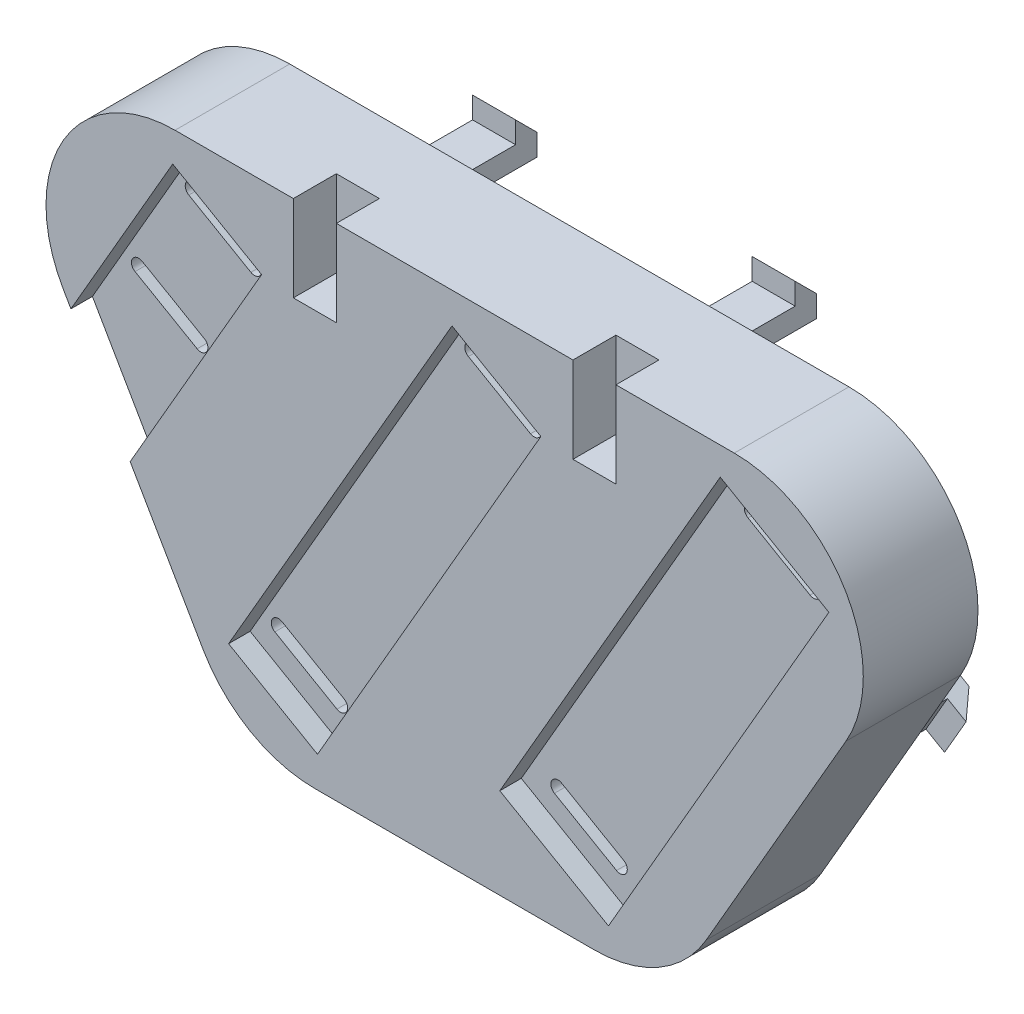
SolidWorks part; units mm, degrees
ref_plane "Front Plane" through (0, 0, 0) normal (0, 0, 1) x (1, 0, 0)
ref_plane "Top Plane" through (0, 0, 0) normal (0, 1, 0) x (1, 0, 0)
ref_plane "Right Plane" through (0, 0, 0) normal (1, 0, 0) x (0, 0, -1)
sketch "Sketch1" plane through (0, 0, 0) normal (0, 0, 1) x (1, 0, 0)
  line L0 (0, 0) -> (-19.5, 0) construction
  line L1 (-9.75, -16.8875) -> (-29.25, -16.8875) construction
  line L2 (0, 0) -> (-9.75, -16.8875) construction
  line L3 (-9.75, -16.8875) -> (-19.5, 0) construction
  line L4 (-19.5, 0) -> (-29.25, -16.8875) construction
  line L5 (-29.25, -16.8875) -> (-39, 0) construction
  line L6 (-39, 0) -> (-19.5, 0) construction
  line L7 (8.9827, 0.5584) -> (-5.4199, -24.3875) construction
  line L8 (-5.4199, -24.3875) -> (-33.5801, -24.3875) construction
  line L9 (-33.5801, -24.3875) -> (-47.9827, 0.5584) construction
  line L10 (-43.9749, 7.5) -> (4.9749, 7.5) construction
  line L11 (7.7942, -4.5) -> (-1.9558, -21.3875)
  line L12 (-9.75, -25.8875) -> (-29.25, -25.8875)
  line L13 (-37.0442, -21.3875) -> (-46.7942, -4.5)
  line L14 (-39, 9) -> (0, 9)
  line L15 (1.7814, -11.9145) -> (3.0804, -12.6645) construction
  line L16 (-19.5, -24.3875) -> (-19.5, -25.8875) construction
  line L17 (-40.7814, -11.9145) -> (-42.0804, -12.6645) construction
  line L18 (-19.5, 7.5) -> (-19.5, 9) construction
  circle A0 centre (-29.25, -16.8875) radius 7.5
  circle A1 centre (-19.5, 0) radius 7.5
  circle A2 centre (0, 0) radius 7.5
  circle A3 centre (0, 0) radius 7.5
  circle A4 centre (-9.75, -16.8875) radius 7.5
  circle A5 centre (-39, 0) radius 7.5
  arc A6 (7.7942, -4.5) -> (0, 9) centre (0, 0) ccw
  arc A7 (-39, 9) -> (-46.7942, -4.5) centre (-39, 0) ccw
  arc A8 (-1.9558, -21.3875) -> (-9.75, -25.8875) centre (-9.75, -16.8875) cw
  arc A9 (-29.25, -25.8875) -> (-37.0442, -21.3875) centre (-29.25, -16.8875) cw
  point P28 (1.7814, -11.9145)
  point P30 (-19.5, -24.3875)
  point P32 (-40.7814, -11.9145)
  point P35 (-19.5, 9)
  dimension "D2" = 15
  dimension "D3" = 19.5
  dimension "D4" = 1.5
  dimension "D5" = 1.5
  dimension "D1" = 0.25
extrude "Boss-Extrude1" add sketch "Sketch1" along normal blind 5
sketch "Sketch2" plane through (0, 0, 5) normal (0, 0, 1) x (1, 0, 0)
  line L0 (-1.9558, -21.3875) -> (7.7942, -4.5) construction
  line L1 (0, 9) -> (-39, 9) construction
  line L2 (-46.7942, -4.5) -> (-37.0442, -21.3875) construction
  line L3 (-29.25, -25.8875) -> (-9.75, -25.8875) construction
  line L4 (-1.9558, -21.3875) -> (7.7942, -4.5)
  line L5 (0, 9) -> (-39, 9)
  line L6 (-46.7942, -4.5) -> (-37.0442, -21.3875)
  line L7 (-29.25, -25.8875) -> (-9.75, -25.8875)
  line L8 (4.0401, 1.9976) -> (-0.2901, 4.4976) construction
  line L9 (3.7901, 1.5646) -> (-0.5401, 4.0646)
  line L10 (4.2901, 2.4306) -> (-0.0401, 4.9306)
  line L11 (-9.4599, -21.3851) -> (-13.7901, -18.8851) construction
  line L12 (-9.7099, -21.8181) -> (-14.0401, -19.3181)
  line L13 (-9.2099, -20.9521) -> (-13.5401, -18.4521)
  line L14 (1.875, 3.2476) -> (-11.625, -20.1351) construction
  line L15 (-31.125, -20.1351) -> (-29.25, -16.8875) construction
  line L16 (0, 0) -> (1.875, 3.2476) construction
  line L17 (1.875, 3.2476) -> (3.75, 6.4952) construction
  line L18 (-11.625, -20.1351) -> (-13.5, -23.3827) construction
  line L19 (-11.625, -20.1351) -> (-9.75, -16.8875) construction
  line L20 (-17.625, 3.2476) -> (-15.75, 6.4952) construction
  line L21 (-17.625, 3.2476) -> (-31.125, -20.1351) construction
  line L22 (-19.5, 0) -> (-17.625, 3.2476) construction
  line L23 (-31.125, -20.1351) -> (-33, -23.3827) construction
  line L24 (-15.4599, 1.9976) -> (-19.7901, 4.4976) construction
  line L25 (-15.7099, 1.5646) -> (-20.0401, 4.0646)
  line L26 (-15.2099, 2.4306) -> (-19.5401, 4.9306)
  line L27 (-28.9599, -21.3851) -> (-33.2901, -18.8851) construction
  line L28 (-29.2099, -21.8181) -> (-33.5401, -19.3181)
  line L29 (-28.7099, -20.9521) -> (-33.0401, -18.4521)
  line L30 (-34.9599, 1.9976) -> (-39.2901, 4.4976) construction
  line L31 (-35.2099, 1.5646) -> (-39.5401, 4.0646)
  line L32 (-34.7099, 2.4306) -> (-39.0401, 4.9306)
  line L33 (-38.7099, -4.4976) -> (-43.0401, -1.9976) construction
  line L34 (-38.9599, -4.9306) -> (-43.2901, -2.4306)
  line L35 (-38.4599, -4.0646) -> (-42.7901, -1.5646)
  line L36 (-37.125, 3.2476) -> (-40.875, -3.2476) construction
  line L37 (-37.125, 3.2476) -> (-35.25, 6.4952) construction
  line L38 (-40.875, -3.2476) -> (-42.75, -6.4952) construction
  line L39 (-37.125, 3.2476) -> (-39, 0) construction
  arc A0 (-9.75, -25.8875) -> (-1.9558, -21.3875) centre (-9.75, -16.8875) ccw construction
  arc A1 (7.7942, -4.5) -> (0, 9) centre (0, 0) ccw construction
  arc A2 (-39, 9) -> (-46.7942, -4.5) centre (-39, 0) ccw construction
  arc A3 (-37.0442, -21.3875) -> (-29.25, -25.8875) centre (-29.25, -16.8875) ccw construction
  arc A4 (-9.75, -25.8875) -> (-1.9558, -21.3875) centre (-9.75, -16.8875) ccw
  arc A5 (7.7942, -4.5) -> (0, 9) centre (0, 0) ccw
  arc A6 (-39, 9) -> (-46.7942, -4.5) centre (-39, 0) ccw
  arc A7 (-37.0442, -21.3875) -> (-29.25, -25.8875) centre (-29.25, -16.8875) ccw
  circle A8 centre (-39, 0) radius 7.5 construction
  circle A9 centre (-29.25, -16.8875) radius 7.5 construction
  circle A10 centre (-19.5, 0) radius 7.5 construction
  circle A11 centre (-9.75, -16.8875) radius 7.5 construction
  circle A12 centre (0, 0) radius 7.5 construction
  circle A13 centre (-39, 0) radius 7.5
  circle A14 centre (-29.25, -16.8875) radius 7.5
  circle A15 centre (-19.5, 0) radius 7.5
  circle A16 centre (-9.75, -16.8875) radius 7.5
  circle A17 centre (0, 0) radius 7.5
  arc A18 (3.7901, 1.5646) -> (4.2901, 2.4306) centre (4.0401, 1.9976) ccw
  arc A19 (-0.0401, 4.9306) -> (-0.5401, 4.0646) centre (-0.2901, 4.4976) ccw
  arc A20 (-9.7099, -21.8181) -> (-9.2099, -20.9521) centre (-9.4599, -21.3851) ccw
  arc A21 (-13.5401, -18.4521) -> (-14.0401, -19.3181) centre (-13.7901, -18.8851) ccw
  arc A22 (-15.7099, 1.5646) -> (-15.2099, 2.4306) centre (-15.4599, 1.9976) ccw
  arc A23 (-19.5401, 4.9306) -> (-20.0401, 4.0646) centre (-19.7901, 4.4976) ccw
  arc A24 (-29.2099, -21.8181) -> (-28.7099, -20.9521) centre (-28.9599, -21.3851) ccw
  arc A25 (-33.0401, -18.4521) -> (-33.5401, -19.3181) centre (-33.2901, -18.8851) ccw
  arc A26 (-35.2099, 1.5646) -> (-34.7099, 2.4306) centre (-34.9599, 1.9976) ccw
  arc A27 (-39.0401, 4.9306) -> (-39.5401, 4.0646) centre (-39.2901, 4.4976) ccw
  arc A28 (-38.9599, -4.9306) -> (-38.4599, -4.0646) centre (-38.7099, -4.4976) ccw
  arc A29 (-42.7901, -1.5646) -> (-43.2901, -2.4306) centre (-43.0401, -1.9976) ccw
  point P8 (-37.125, 3.2476)
  point P25 (1.875, 3.2476)
  point P32 (-11.625, -20.1351)
  point P45 (-17.625, 3.2476)
  point P52 (-31.125, -20.1351)
  point P64 (-40.875, -3.2476)
  circle M1 centre (-9.75, -16.8875) radius 7.5
  circle M2 centre (0, 0) radius 7.5
  arc M3 (7.7942, -4.5) -> (0, 9) centre (0, 0) ccw
  line M4 (0, 9) -> (-39, 9)
  arc M5 (-39, 9) -> (-46.7942, -4.5) centre (-39, 0) ccw
  line M6 (-46.7942, -4.5) -> (-37.0442, -21.3875)
  arc M7 (-37.0442, -21.3875) -> (-29.25, -25.8875) centre (-29.25, -16.8875) ccw
  line M8 (-29.25, -25.8875) -> (-9.75, -25.8875)
  arc M9 (-9.75, -25.8875) -> (-1.9558, -21.3875) centre (-9.75, -16.8875) ccw
  line M10 (-1.9558, -21.3875) -> (7.7942, -4.5)
  circle M11 centre (-19.5, 0) radius 7.5
  circle M12 centre (-29.25, -16.8875) radius 7.5
  circle M13 centre (-39, 0) radius 7.5
  dimension "D1" = 1
  dimension "D2" = 5
extrude "Boss-Extrude2" add sketch "Sketch2" along normal blind 1.5 contours A21 L13 A20 L12 M1 | M10 M3 M4 M5 M6 M7 M8 M9 M2 M11 M13 M12 M1 | A19 L10 A18 L9 M2 | A23 L26 A22 L25 M11 | A25 L29 A24 L28 M12 | A29 L35 A28 L34 A27 L32 A26 L31 M13 region at (-5.5841, -24.103, 5) region at (-39, 0, 5) region at (-29.1865, -16.7776, 5) region at (-19.5635, -0.1099, 5) region at (-9.6865, -16.7776, 5) region at (-0.0635, -0.1099, 5)
sketch "Sketch3" plane through (0, 0, 6.5) normal (0, 0, 1) x (1, 0, 0)
  line L0 (-46.7942, -4.5) -> (-37.0442, -21.3875) construction
  line L1 (-29.25, -25.8875) -> (-9.75, -25.8875) construction
  line L2 (-1.9558, -21.3875) -> (7.7942, -4.5) construction
  line L3 (0, 9) -> (-39, 9) construction
  line L4 (-46.7942, -4.5) -> (-37.0442, -21.3875)
  line L5 (-29.25, -25.8875) -> (-9.75, -25.8875)
  line L6 (-1.9558, -21.3875) -> (7.7942, -4.5)
  line L7 (0, 9) -> (-39, 9)
  line L8 (6.6014, 2.6839) -> (-8.7736, -23.9464)
  line L9 (6.6014, 2.6839) -> (-0.9764, 7.0589)
  line L10 (-8.7736, -23.9464) -> (-16.3514, -19.5714)
  line L11 (-0.9764, 7.0589) -> (-16.3514, -19.5714)
  line L12 (6.6014, 2.6839) -> (-16.3514, -19.5714) construction
  line L13 (-8.7736, -23.9464) -> (-0.9764, 7.0589) construction
  line L14 (-11.625, -20.1351) -> (-13.5, -23.3827) construction
  line L15 (-11.625, -20.1351) -> (-13.5, -23.3827) construction
  line L16 (-11.875, -20.5681) -> (-12.5625, -21.7589) construction
  line L17 (-9.7099, -21.8181) -> (-14.0401, -19.3181) construction
  line L18 (-14.2231, -18.6351) -> (-15.4139, -17.9476) construction
  line L19 (1.875, 3.2476) -> (-11.625, -20.1351) construction
  line L20 (1.875, 3.2476) -> (-11.625, -20.1351) construction
  line L21 (-31.125, -20.1351) -> (-33, -23.3827) construction
  line L22 (-17.625, 3.2476) -> (-31.125, -20.1351) construction
  line L23 (-31.125, -20.1351) -> (-33, -23.3827) construction
  line L24 (-17.625, 3.2476) -> (-31.125, -20.1351) construction
  line L25 (-13.4854, 3.2587) -> (-29.0648, -23.7257)
  line L26 (-13.4854, 3.2587) -> (-19.6852, 6.8382)
  line L27 (-29.0648, -23.7257) -> (-35.2646, -20.1462)
  line L28 (-19.6852, 6.8382) -> (-35.2646, -20.1462)
  line L29 (-13.4854, 3.2587) -> (-35.2646, -20.1462) construction
  line L30 (-29.0648, -23.7257) -> (-19.6852, 6.8382) construction
  line L31 (-32.8571, -19.1351) -> (-34.2249, -18.3454) construction
  line L32 (-31.375, -20.5681) -> (-32.1647, -21.9359) construction
  line L33 (-29.2099, -21.8181) -> (-33.5401, -19.3181) construction
  line L34 (-32.9626, 3.2982) -> (-42.1296, -12.5794)
  line L35 (-32.9626, 3.2982) -> (-39.1624, 6.8776)
  line L37 (-39.1624, 6.8776) -> (-46.2627, -5.4206)
  line L38 (-32.9626, 3.2982) -> (-45.5024, -6.7376) construction
  line L39 (-42.1296, -12.5794) -> (-39.1624, 6.8776) construction
  line L40 (-37.125, 3.2476) -> (-40.875, -3.2476) construction
  line L41 (-36.875, 3.6806) -> (-36.0625, 5.0879) construction
  line L42 (-34.7099, 2.4306) -> (-39.0401, 4.9306) construction
  line L43 (-36.0625, 5.0879) -> (-35.25, 6.4952) construction
  arc A0 (-37.0442, -21.3875) -> (-29.25, -25.8875) centre (-29.25, -16.8875) ccw construction
  arc A1 (-9.75, -25.8875) -> (-1.9558, -21.3875) centre (-9.75, -16.8875) ccw construction
  arc A2 (7.7942, -4.5) -> (0, 9) centre (0, 0) ccw construction
  arc A3 (-39, 9) -> (-46.7942, -4.5) centre (-39, 0) ccw construction
  arc A4 (-37.0442, -21.3875) -> (-29.25, -25.8875) centre (-29.25, -16.8875) ccw
  arc A5 (-9.75, -25.8875) -> (-1.9558, -21.3875) centre (-9.75, -16.8875) ccw
  arc A6 (7.7942, -4.5) -> (0, 9) centre (0, 0) ccw
  arc A7 (-39, 9) -> (-46.7942, -4.5) centre (-39, 0) ccw
  arc A8 (-13.5401, -18.4521) -> (-14.0401, -19.3181) centre (-13.7901, -18.8851) ccw construction
  arc A9 (-33.0401, -18.4521) -> (-33.5401, -19.3181) centre (-33.2901, -18.8851) ccw construction
  point P13 (-4.875, -8.4437)
  point P30 (-12.5625, -21.7589)
  point P33 (-4.875, -8.4437)
  point P35 (-24.375, -8.4437)
  point P49 (-24.375, -8.4437)
  point P50 (-40.646, -2.8509)
  line M15 (-1.9558, -21.3875) -> (7.7942, -4.5)
  arc M16 (7.7942, -4.5) -> (0, 9) centre (0, 0) ccw
  line M17 (0, 9) -> (-39, 9)
  arc M18 (-39, 9) -> (-46.7942, -4.5) centre (-39, 0) ccw
  line M19 (-46.7942, -4.5) -> (-37.0442, -21.3875)
  arc M20 (-37.0442, -21.3875) -> (-29.25, -25.8875) centre (-29.25, -16.8875) ccw
  line M21 (-29.25, -25.8875) -> (-9.75, -25.8875)
  arc M22 (-9.75, -25.8875) -> (-1.9558, -21.3875) centre (-9.75, -16.8875) ccw
extrude "Boss-Extrude3" add sketch "Sketch3" along normal blind 1.5 contours L37 L35 L34 L4 L28 L26 L25 L27 L11 L9 L8 L10 M20 M21 M22 M15 M16 M17 M18 M19 region at (-46.2155, 4.1659, 6.5)
sketch "Sketch4" plane through (0, 0, 0) normal (0, 0, -1) x (-1, 0, 0)
  line L0 (29.25, -25.8875) -> (9.75, -25.8875) construction
  line L1 (21, -25.8875) -> (18, -25.8875)
  line L2 (21, -25.8875) -> (21, -22.8875)
  line L3 (21, -22.8875) -> (18, -22.8875)
  line L4 (18, -25.8875) -> (18, -22.8875)
  line L5 (21, -25.8875) -> (18, -22.8875) construction
  line L6 (21, -22.8875) -> (18, -25.8875) construction
  line L7 (29.25, -25.8875) -> (9.75, -25.8875)
  line L8 (0, 9) -> (39, 9) construction
  line L9 (46.7942, -4.5) -> (37.0442, -21.3875) construction
  line L10 (1.9558, -21.3875) -> (-7.7942, -4.5) construction
  line L11 (0, 9) -> (39, 9)
  line L12 (46.7942, -4.5) -> (37.0442, -21.3875)
  line L13 (1.9558, -21.3875) -> (-7.7942, -4.5)
  line L14 (40.0712, -10.1447) -> (42.6692, -11.6447)
  line L15 (40.0712, -10.1447) -> (38.5712, -12.7428)
  line L16 (42.6692, -11.6447) -> (41.1692, -14.2428)
  line L17 (38.5712, -12.7428) -> (41.1692, -14.2428)
  line L18 (40.0712, -10.1447) -> (41.1692, -14.2428) construction
  line L19 (42.6692, -11.6447) -> (38.5712, -12.7428) construction
  line L20 (-1.0712, -10.1447) -> (-3.6692, -11.6447)
  line L21 (-1.0712, -10.1447) -> (0.4288, -12.7428)
  line L22 (-3.6692, -11.6447) -> (-2.1692, -14.2428)
  line L23 (0.4288, -12.7428) -> (-2.1692, -14.2428)
  line L24 (-1.0712, -10.1447) -> (-2.1692, -14.2428) construction
  line L25 (-3.6692, -11.6447) -> (0.4288, -12.7428) construction
  line L26 (41.9192, -12.9437) -> (3.9115, 9) construction
  line L27 (11.25, 6) -> (8.25, 6)
  line L28 (11.25, 6) -> (11.25, 9)
  line L29 (11.25, 9) -> (8.25, 9)
  line L30 (8.25, 6) -> (8.25, 9)
  line L31 (11.25, 6) -> (8.25, 9) construction
  line L32 (11.25, 9) -> (8.25, 6) construction
  line L33 (30.75, 6) -> (27.75, 6)
  line L34 (30.75, 6) -> (30.75, 9)
  line L35 (30.75, 9) -> (27.75, 9)
  line L36 (27.75, 6) -> (27.75, 9)
  line L37 (30.75, 6) -> (27.75, 9) construction
  line L38 (30.75, 9) -> (27.75, 6) construction
  line L39 (-2.9192, -12.9437) -> (35.0885, 9) construction
  point P0 (19.5, -24.3875)
  point P5 (9.75, 7.5)
  point P8 (19.5, -25.8875)
  point P15 (40.6202, -12.1937)
  point P16 (-1.6202, -12.1937)
  point P29 (29.25, 7.5)
  line M35 (9.75, -25.8875) -> (29.25, -25.8875)
  dimension "D1" = 3
  dimension "D2" = 3
extrude "Boss-Extrude4" add sketch "Sketch4" along normal blind 6 contours L15 L17 L12 L14 | L4 L2 L3 M35 | L23 L21 L20 L13 | L30 L27 L28 L11 | L36 L33 L34 L11 region at (-19.5, -24.3875, 0) region at (-29.25, 7.5, 0) region at (-9.75, 7.5, 0) region at (-40.6202, -12.1937, 0) region at (1.6202, -12.1937, 0)
sketch "Sketch5" plane through (-5.625, 9.7428, 0) normal (-0.5, 0.866, 0) x (0.866, 0.5, 0)
  line L0 (-42.775, 6) -> (-39.775, 6) construction
  line L1 (-42.775, 0) -> (-41.275, 0)
  line L2 (-42.775, 0) -> (-42.775, 4.5)
  line L3 (-42.775, 4.5) -> (-41.275, 4.5)
  line L4 (-41.275, 0) -> (-41.275, 4.5)
  line L5 (-42.775, 4.5) -> (-41.275, 6)
  point P9 (-41.275, 6)
  line M2 (-42.775, 0) -> (-39.775, 0)
  line M4 (-39.775, 6) -> (-42.775, 6)
  line M5 (-42.775, 6) -> (-42.775, 0)
  dimension "D1" = 4.5
extrude "Cut-Extrude1" cut sketch "Sketch5" against normal up to next contours L4 L3 M2 M5 | L5 M5 M4 region at (-42.0197, -11.2697, -2.25) region at (-42.2362, -11.3947, -5.5)
sketch "Sketch7" plane through (-30.75, 0, 0) normal (-1, 0, 0) x (0, 0, 1)
  line L0 (-6, 6) -> (-6, 9) construction
  line L1 (0, 9) -> (-4.5, 9)
  line L2 (0, 9) -> (0, 7.5)
  line L3 (0, 7.5) -> (-4.5, 7.5)
  line L4 (-4.5, 9) -> (-4.5, 7.5)
  line L5 (-4.5, 9) -> (-6, 7.5)
  point P9 (-6, 7.5)
  line M3 (0, 6) -> (0, 9)
  line M4 (0, 9) -> (-6, 9)
  line M5 (-6, 9) -> (-6, 6)
  dimension "D1" = 4.5
extrude "Cut-Extrude2" cut sketch "Sketch7" against normal up to next contours L4 L3 M4 M3 | L5 M4 M5 region at (-30.75, 8.25, -2.25) region at (-30.75, 8.5, -5.5)
ref_axis "Axis1" through (-19.5, -25.8875, -6) along (0, 0, 1)
ref_plane "Plane1" through (-19.5, 0, 0) normal (-1, 0, 0) x (0, 0, 1)
mirror "Mirror1" about plane through (-19.5, 0, 0) normal (-1, 0, 0) of "Cut-Extrude2", "Cut-Extrude1"
sketch "Sketch8" plane through (-21, 0, 0) normal (-1, 0, 0) x (0, 0, 1)
  line L0 (-4.5, -25.8875) -> (-6, -24.3875)
  line L1 (0, -25.8875) -> (-4.5, -25.8875)
  line L2 (0, -25.8875) -> (0, -24.3875)
  line L3 (0, -24.3875) -> (-4.5, -24.3875)
  line L4 (-4.5, -25.8875) -> (-4.5, -24.3875)
  line L5 (0, -25.8875) -> (0, -22.8875) construction
  line L6 (-6, -25.8875) -> (-6, -22.8875) construction
  line M2 (0, -25.8875) -> (0, -22.8875)
  line M4 (-6, -22.8875) -> (-6, -25.8875)
  line M5 (-6, -25.8875) -> (0, -25.8875)
  dimension "D1" = 4.5
extrude "Cut-Extrude3" cut sketch "Sketch8" against normal up to next contours L0 M5 M4 | L4 L3 M5 M2 region at (-21, -25.3875, -5.5) region at (-21, -25.1375, -2.25)
sketch "Sketch9" plane through (0, 0, 8) normal (0, 0, 1) x (1, 0, 0)
  line L0 (-39, 9) -> (-19.5, 9)
  line L1 (0, 9) -> (-39, 9) construction
  line L2 (-19.5, 9) -> (0, 9) construction
  line L3 (-29.25, 9) -> (-29.25, 3) construction
  line L4 (-27.75, 3) -> (-30.75, 3)
  line L5 (-27.75, 3) -> (-27.75, 9)
  line L6 (-27.75, 9) -> (-30.75, 9)
  line L7 (-30.75, 3) -> (-30.75, 9)
  line L8 (-27.75, 3) -> (-30.75, 9) construction
  line L9 (-27.75, 9) -> (-30.75, 3) construction
  line L10 (-8.25, 3) -> (-11.25, 3)
  line L11 (-8.25, 3) -> (-8.25, 9)
  line L12 (-8.25, 9) -> (-11.25, 9)
  line L13 (-11.25, 3) -> (-11.25, 9)
  line L14 (-8.25, 3) -> (-11.25, 9) construction
  line L15 (-8.25, 9) -> (-11.25, 3) construction
  line L16 (-9.75, 9) -> (-9.75, 3) construction
  point P5 (-29.25, 6)
  point P12 (-9.75, 6)
  point P21 (0, 0)
  point P22 (0, 0)
  point P23 (0, 0)
  point P24 (0, 0)
  point P25 (0, 0)
  dimension "D1" = 3
  dimension "D2" = 6
extrude "Cut-Extrude4" cut sketch "Sketch9" against normal blind 3 contours L10 L13 L12 L11 | L4 L7 L6 L5
equation "\"D3@Sketch1\"=\"D2@Sketch1\"+4.5"
equation "\"D1@Sketch2\"=.65+.35"
